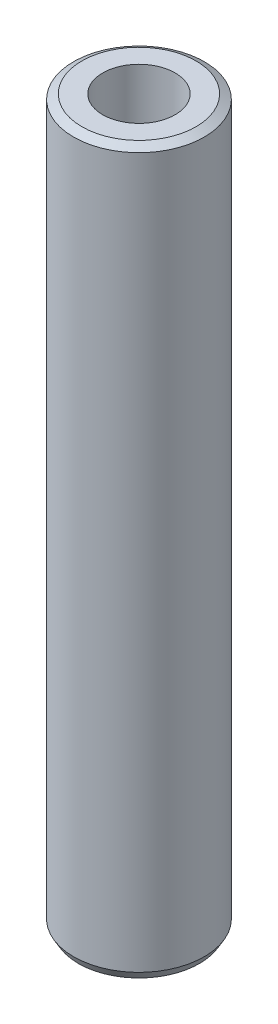
SolidWorks part; units mm, degrees
ref_plane "Front Plane" through (0, 0, 0) normal (0, 0, 1) x (1, 0, 0)
ref_plane "Top Plane" through (0, 0, 0) normal (0, 1, 0) x (1, 0, 0)
ref_plane "Right Plane" through (0, 0, 0) normal (1, 0, 0) x (0, 0, -1)
sketch "Sketch1" plane through (0, 0, 0) normal (0, 1, 0) x (1, 0, 0)
  circle A0 centre (0, 0) radius 7.5
  dimension "SHAFT_OD" = 15
extrude "Boss-Extrude1" add sketch "Sketch1" along normal blind 82.964
sketch "Sketch2" plane through (0, 0, 0) normal (0, 1, 0) x (1, 0, 0)
  circle A0 centre (0, 0) radius 4.158
  dimension "BORE_D" = 8.316
extrude "Cut-Extrude1" cut sketch "Sketch2" along normal through all
chamfer "Chamfer1" distance 0.5497 angle 60 2 edges at (0, 82.964, 7.5) (0, 0, 7.5) first distance on face at (0, 82.964, 7.5) first distance on face at (0, 0, 4.158)
